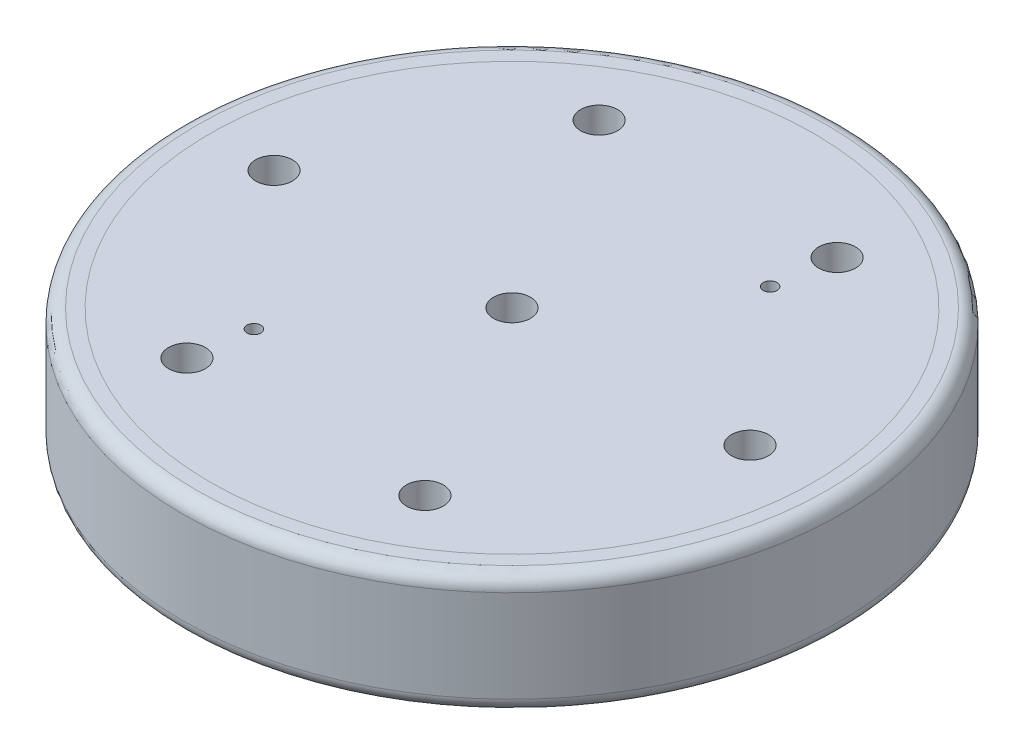
SolidWorks part; units mm, degrees
ref_plane "Alzado" through (0, 0, 0) normal (0, 0, 1) x (1, 0, 0)
ref_plane "Planta" through (0, 0, 0) normal (0, 1, 0) x (1, 0, 0)
ref_plane "Vista lateral" through (0, 0, 0) normal (1, 0, 0) x (0, 0, -1)
sketch "Croquis1" plane through (0, 0, 0) normal (0, 1, 0) x (1, 0, 0)
  circle A0 centre (0, 0) radius 32.75
  dimension "D1" = 65.5
extrude "Saliente-Extruir1" add sketch "Croquis1" along normal blind 3
sketch "Croquis2" plane through (0, 3, 0) normal (0, 1, 0) x (1, 0, 0)
  circle A0 centre (0, 0) radius 2
extrude "Cortar-Extruir1" cut sketch "Croquis2" against normal blind 4
sketch "Croquis7" plane through (0, 3, 0) normal (0, 1, 0) x (1, 0, 0)
  line L2 (25.8141, 0) -> (12.907, 22.3556)
  line L3 (12.907, 22.3556) -> (-12.907, 22.3556)
  line L4 (-12.907, 22.3556) -> (-25.8141, 0)
  line L5 (-25.8141, 0) -> (-12.907, -22.3556)
  line L6 (-12.907, -22.3556) -> (12.907, -22.3556)
  line L7 (12.907, -22.3556) -> (25.8141, 0)
  circle A0 centre (25.8141, 0) radius 2
  circle A4 centre (-25.8141, 0) radius 2
  circle A5 centre (0, 0) radius 22.3556 construction
  circle A6 centre (12.907, 22.3556) radius 2
  circle A7 centre (-12.907, -22.3556) radius 2
  circle A8 centre (-12.907, 22.3556) radius 2
  circle A9 centre (12.907, -22.3556) radius 2
extrude "Cortar-Extruir4" cut sketch "Croquis7" against normal blind 10 contours A8 L4 L3 | A4 L4 L5 | A4 L5 L4 | A8 L3 L4 | L2 A6 L3 | L3 A6 L2 | L7 A0 L2 | L2 A0 L7 | A7 L5 L6 | A7 L6 L5 | L6 A9 L7 | L7 A9 L6 | A4 region at (24.7114, 3, 0) region at (26.3654, 3, 0) region at (12.3557, 3, -21.4007) region at (13.1827, 3, -22.8331) region at (13.1827, 3, 22.8331) region at (12.3557, 3, 21.4007) region at (-12.3557, 3, -21.4007) region at (-13.1827, 3, -22.8331) region at (-13.1827, 3, 22.8331) region at (-12.3557, 3, 21.4007) region at (-24.7114, 3, 0) region at (-26.3654, 3, 0)
sketch "Croquis8" plane through (0, 3, 0) normal (0, 1, 0) x (1, 0, 0)
  circle A0 centre (0, 0) radius 32.75
  circle A1 centre (0, 0) radius 35.75
extrude "Saliente-Extruir2" add sketch "Croquis8" against normal blind 13 separate body
fillet "Redondeo1" radius 1.5 3 edges at (0, -10, 32.75) (0, -10, 35.75) (0, 3, 35.75)
sketch "Croquis9" plane through (0, 3, 0) normal (0, 1, 0) x (1, 0, 0)
  line L0 (0, 0) -> (12, 0)
  line L1 (12, 0) -> (12, 16)
  line L2 (0, 0) -> (-12, 0)
  line L3 (-12, 0) -> (-12, -16)
  circle A0 centre (12, 16) radius 0.75
  circle A1 centre (-12, -16) radius 0.75
extrude "Cortar-Extruir5" cut sketch "Croquis9" against normal blind 10 contours A0 | A1 region at (11.4847, 3, -16.5153) region at (-11.4847, 3, 15.4847)
